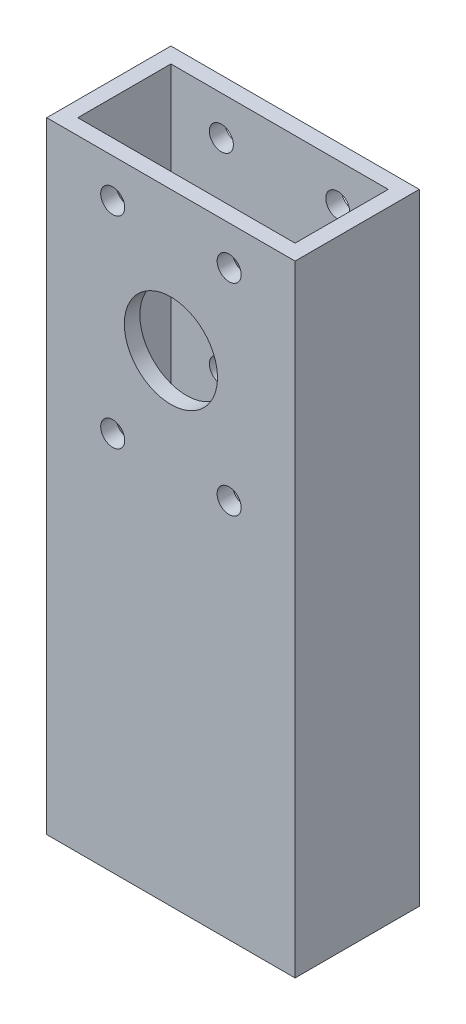
SolidWorks part; units mm, degrees
material "6061-T6 (SS)"
ref_plane "Front" through (0, 0, 0) normal (0, 0, 1) x (1, 0, 0)
ref_plane "Top" through (0, 0, 0) normal (0, 1, 0) x (1, 0, 0)
ref_plane "Right" through (0, 0, 0) normal (1, 0, 0) x (0, 0, -1)
sketch "Sketch1" plane through (0, 0, 0) normal (0, 1, 0) x (1, 0, 0)
  line L1 (-25.4, -12.7) -> (25.4, -12.7)
  line L2 (-25.4, -12.7) -> (-25.4, 12.7)
  line L3 (-25.4, 12.7) -> (25.4, 12.7)
  line L4 (25.4, -12.7) -> (25.4, 12.7)
  line L5 (-25.4, -12.7) -> (25.4, 12.7) construction
  line L6 (-25.4, 12.7) -> (25.4, -12.7) construction
  point P0 (0, 0)
  dimension "D1" = 25.4
  dimension "D2" = 50.8
extrude "Extrude-Thin1" add sketch "Sketch1" along normal blind 127 thin thin type one direction reverse wall 3.175
sketch "Sketch2" plane through (0, 0, -12.7) normal (0, 0, -1) x (-1, 0, 0)
  line L0 (0, 127) -> (0, 95.25)
  line L1 (-25.4, 127) -> (25.4, 127) construction
  line L3 (0, 85.725) -> (0, 104.775) construction
  circle A1 centre (0, 95.25) radius 23.8125
  circle A3 centre (0, 95.25) radius 9.525
  point P5 (0, 0)
  point P12 (0, 95.25)
  dimension "D1" = 19.05
  dimension "D3" = 47.625
  dimension "D2" = 31.75
hole_wizard "#10 (0.1935) Diameter Hole2" positions "Sketch5" profile "Sketch6" hole size "#10" standard "ANSI Inch" end condition through all
sketch "Sketch5" plane through (0, 0, -12.7) normal (0, 0, -1) x (-1, 0, 0)
  line L0 (0, 127) -> (0, 98.425)
  line L1 (-25.4, 127) -> (25.4, 127) construction
  line L3 (-11.9063, 119.0472) -> (11.9063, 119.0472)
  line L4 (-11.9063, 119.0472) -> (-11.9063, 77.8028)
  line L5 (-11.9063, 77.8028) -> (11.9063, 77.8028)
  line L6 (11.9063, 119.0472) -> (11.9063, 77.8028)
  circle A0 centre (0, 98.425) radius 23.8125
  point P21 (-11.9063, 119.0472)
  point P22 (11.9063, 119.0472)
  point P24 (11.9063, 77.8028)
  point P25 (-11.9062, 77.8028)
  point P123 (11.9063, 119.0472)
  point P124 (-11.9063, 134.1121)
  point P125 (11.9063, 119.0472)
  dimension "D1" = 47.625
  dimension "D2" = 28.575
  dimension "D3" = 23.8125
sketch "Sketch6" plane through (11.9062, 77.8028, -12.7) normal (1, 0, 0) x (0, 1, 0)
  line L0 (0, 0) -> (0, 25.4)
  line L1 (0, 25.4) -> (2.4574, 25.4)
  line L2 (2.4574, 25.4) -> (2.4574, 0)
  line L5 (2.4574, 0) -> (0, 0)
  line L11 (0, -6.35) -> (0, 107.95) construction
  dimension "Thru Hole Dia." = 4.9149
  dimension "Thru Hole Depth" = 25.4
sketch "Sketch7" plane through (0, 0, -12.7) normal (0, 0, -1) x (-1, 0, 0)
  line L0 (-11.9063, 119.0472) -> (11.9063, 77.8028) construction
  circle A1 centre (0, 98.425) radius 9.525
  point P7 (-0.5444, 99.368)
  point P8 (2.8501, 93.4885)
  point P9 (0, 98.425)
  dimension "D1" = 19.05
extrude "Cut-Extrude2" cut sketch "Sketch7" against normal through all both
